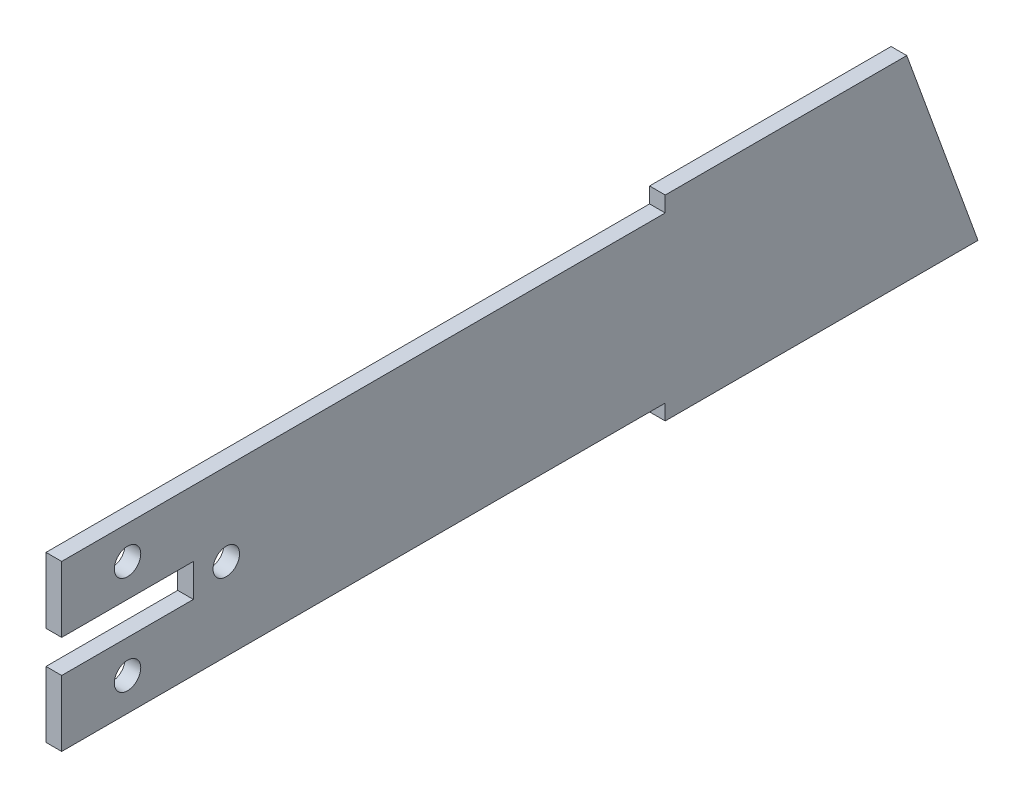
SolidWorks part; units mm, degrees
material "AISI Type A2 Tool Steel"
ref_plane "Front Plane" through (0, 0, 0) normal (0, 0, 1) x (1, 0, 0)
ref_plane "Top Plane" through (0, 0, 0) normal (0, 1, 0) x (1, 0, 0)
ref_plane "Right Plane" through (0, 0, 0) normal (1, 0, 0) x (0, 0, -1)
other "Bounding Box"
ref_plane "Default Plane" through (-8.9266, -12.7485, 0) normal (-0.1736, 0.9848, 0) x (0.9848, 0.1736, 0)
sketch "Sketch2" plane through (0, 0, 0) normal (1, 0, 0) x (0, 0, -1)
  line L0 (0, 0) -> (0, 12.7)
  line L1 (0, 12.7) -> (25.4, 12.7)
  line L2 (25.4, 12.7) -> (25.4, 19.05)
  line L3 (25.4, 19.05) -> (0, 19.05)
  line L4 (0, 19.05) -> (0, 31.75)
  line L5 (0, 31.75) -> (38.1, 31.75)
  line L6 (38.1, 31.75) -> (38.1, 0) construction
  line L7 (38.1, 0) -> (0, 0)
  line L8 (38.1, 31.75) -> (116.4082, 31.75)
  line L10 (116.4082, 0) -> (38.1, 0)
  line L11 (116.4082, 0) -> (116.4082, 31.75) construction
  line L12 (116.4082, 31.75) -> (116.4082, 34.7472)
  line L13 (116.4082, 34.7472) -> (162.9954, 34.7472)
  line L14 (162.9954, 34.7472) -> (176.7332, -2.9972)
  line L15 (116.4082, 0) -> (116.4082, -2.9972)
  line L16 (116.4082, -2.9972) -> (176.7332, -2.9972)
  line L17 (12.7, 6.35) -> (31.75, 6.35) construction
  line L18 (31.75, 6.35) -> (31.75, 25.4) construction
  line L19 (31.75, 25.4) -> (12.7, 25.4) construction
  line L20 (12.7, 25.4) -> (12.7, 6.35) construction
  line L21 (12.7, 6.35) -> (12.7, 0) construction
  line L22 (12.7, 6.35) -> (0, 6.35) construction
  line L23 (12.7, 25.4) -> (12.7, 31.75) construction
  line L24 (25.4, 15.875) -> (31.75, 15.875) construction
  line L25 (31.75, 15.875) -> (38.1, 15.875) construction
  circle A0 centre (12.7, 25.4) radius 2.0193
  circle A1 centre (12.7, 6.35) radius 2.0193
  circle A2 centre (31.75, 6.35) radius 2.0193 construction
  circle A3 centre (31.75, 25.4) radius 2.0193 construction
  circle A4 centre (31.75, 15.875) radius 2.0193
  point P23 (12.7, 12.7)
  dimension "D10" = 4.0386
  dimension "D1" = 6.35
  dimension "D2" = 12.7
  dimension "D3" = 25.4
  dimension "D4" = 12.7
  dimension "D5" = 31.75
  dimension "D6" = 116.4082
  dimension "D7" = 2.9972
  dimension "D8" = 70
  dimension "D9" = 60.325
extrude "Boss-Extrude1" [suppressed] add sketch "Sketch2" along normal mid plane 9.525
extrude "Boss-Extrude2" add sketch "Sketch2<2>" along normal blind 3.0226
sketch "Sketch2<2>" plane through (0, 0, 0) normal (1, 0, 0) x (0, 0, -1) same geometry as "Sketch2"
sketch "Sketch3" [suppressed] plane through (4.7625, 0, 0) normal (1, 0, 0) x (0, 0, -1)
  line L1 (194.691, -2.9972) -> (38.1, -2.9972)
  line L2 (194.691, -2.9972) -> (194.691, 34.7472)
  line L3 (194.691, 34.7472) -> (38.1, 34.7472)
  line L4 (38.1, -2.9972) -> (38.1, 34.7472)
  line L6 (180.9532, 34.7472) -> (134.366, 34.7472) construction
  line L7 (25.4, 19.05) -> (25.4, 12.7) construction
  dimension "D1" = 12.7
extrude "Cut-Extrude1" [suppressed] cut sketch "Sketch3" against normal through all
sketch "Sketch4" [suppressed] plane through (0, 31.75, 0) normal (0, 1, 0) x (1, 0, 0)
  line L0 (0, 0) -> (0, 6.35) construction
  line L1 (0, 6.35) -> (0, 19.05) construction
  line L2 (0, 19.05) -> (0, 31.75) construction
  circle A0 centre (0, 19.05) radius 2.5527
  circle A1 centre (0, 6.35) radius 2.0193
  circle A2 centre (0, 31.75) radius 2.0193
  dimension "D1" = 5.1054
  dimension "D4" = 4.0386
  dimension "D2" = 6.35
  dimension "D3" = 12.7
extrude "Cut-Extrude2" [suppressed] cut sketch "Sketch4" against normal through all
sketch "Sketch5" [suppressed] plane through (0, 0, 0) normal (0, -1, 0) x (1, 0, 0)
  circle A0 centre (0, -6.35) radius 2.5527
  circle A1 centre (0, -19.05) radius 2.5527 construction
extrude "Cut-Extrude3" [suppressed] cut sketch "Sketch5" against normal up to next
sketch "Sketch6" plane through (3.0226, 0, 0) normal (1, 0, 0) x (0, 0, -1)
  circle A0 centre (12.7, 25.4) radius 2.5527
  circle A1 centre (31.75, 15.875) radius 2.5527
  circle A2 centre (12.7, 6.35) radius 2.5527
  dimension "D1" = 5.1054
extrude "Cut-Extrude4" cut sketch "Sketch6" against normal through all
